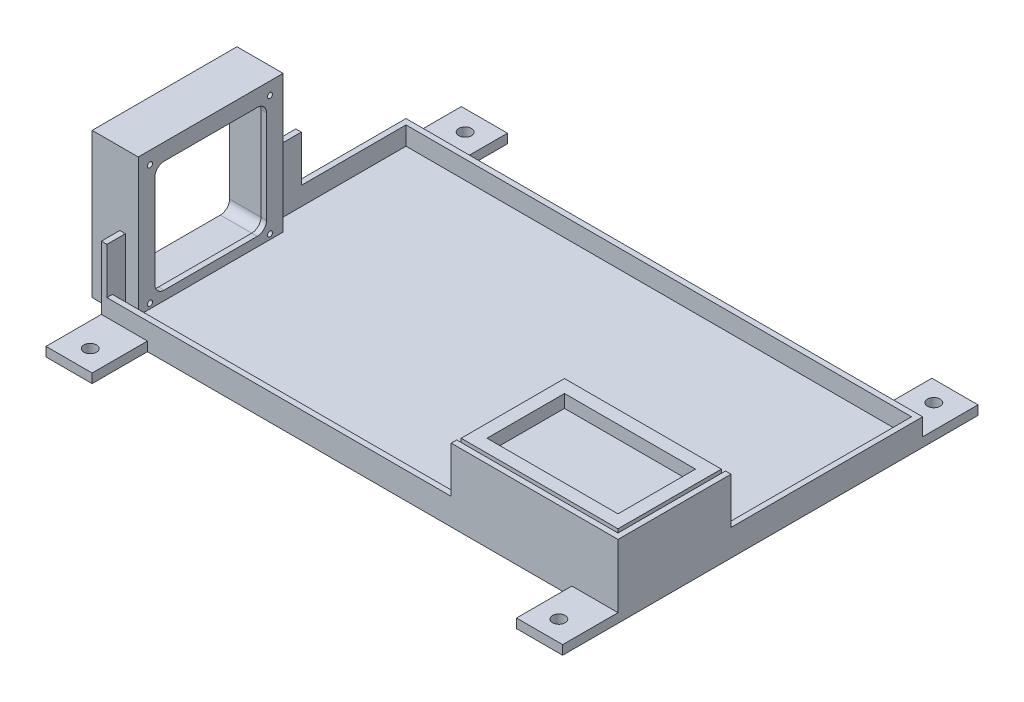
SolidWorks part; units mm, degrees
ref_plane "Front Plane" through (0, 0, 0) normal (0, 0, 1) x (1, 0, 0)
ref_plane "Top Plane" through (0, 0, 0) normal (0, 1, 0) x (1, 0, 0)
ref_plane "Right Plane" through (0, 0, 0) normal (1, 0, 0) x (0, 0, -1)
sketch "Sketch1" plane through (0, 0, 0) normal (0, 1, 0) x (1, 0, 0)
  line L1 (-140, -82.55) -> (140, -82.55)
  line L2 (-140, -82.55) -> (-140, 82.55)
  line L3 (-140, 82.55) -> (140, 82.55)
  line L4 (140, -82.55) -> (140, 82.55)
  line L5 (-140, -82.55) -> (140, 82.55) construction
  line L6 (-140, 82.55) -> (140, -82.55) construction
  point P0 (0, 0)
  dimension "D1" = 165.1
  dimension "D2" = 280
extrude "Floor" add sketch "Sketch1" along normal blind 4.3805
sketch "Sketch2" plane through (0, 4.3805, 0) normal (0, 1, 0) x (1, 0, 0)
  line L0 (137, -79.55) -> (137, 79.55)
  line L1 (137, 79.55) -> (-137, 79.55)
  line L2 (-137, 79.55) -> (-137, -79.55)
  line L3 (-137, -79.55) -> (137, -79.55)
  line L4 (140, -82.55) -> (140, 82.55)
  line L5 (140, 82.55) -> (-140, 82.55)
  line L6 (-140, 82.55) -> (-140, -82.55)
  line L7 (-140, -82.55) -> (140, -82.55)
  line L8 (140, -82.55) -> (140, 82.55)
  line L9 (140, 82.55) -> (-140, 82.55)
  line L10 (-140, 82.55) -> (-140, -82.55)
  line L11 (-140, -82.55) -> (140, -82.55)
  dimension "D1" = 0
  dimension "D2" = 3
extrude "Wall" add sketch "Sketch2" along normal blind 10
sketch "Sketch4" plane through (0, 4.3805, 0) normal (0, 1, 0) x (1, 0, 0)
  line L0 (130, -30.55) -> (59, -30.55)
  line L1 (137, -79.55) -> (52, -79.55)
  line L2 (137, -79.55) -> (137, -23.55)
  line L3 (137, -23.55) -> (52, -23.55)
  line L4 (52, -79.55) -> (52, -23.55)
  line L5 (59, -72.55) -> (59, -30.55)
  line L6 (130, -72.55) -> (59, -72.55)
  line L7 (130, -72.55) -> (130, -30.55)
  dimension "D1" = 85
  dimension "D2" = 56
  dimension "D3" = 7
extrude "Rpi stand" add sketch "Sketch4" along normal blind 7 from offset 30
sketch "Sketch7" plane through (0, 14.3805, 0) normal (0, 1, 0) x (1, 0, 0)
  line L0 (-137, 79.55) -> (-137, -79.55) construction
  line L1 (-140, -82.55) -> (-137, -82.55)
  line L2 (-140, -82.55) -> (-140, 22.7839)
  line L3 (-140, 22.7839) -> (-137, 22.7839)
  line L4 (-137, -82.55) -> (-137, 22.7839)
  line L5 (-137, -79.55) -> (137, -79.55) construction
  line L6 (140, -82.55) -> (49.6123, -82.55)
  line L7 (140, -82.55) -> (140, -79.55)
  line L8 (137, -79.55) -> (49.6123, -79.55)
  line L9 (49.6123, -82.55) -> (49.6123, -79.55)
  line L10 (137, -79.55) -> (137, 79.55) construction
  line L12 (140, -79.55) -> (140, -21.3069)
  line L13 (140, -21.3069) -> (137, -21.3069)
  line L14 (137, -79.55) -> (137, -21.3069)
  line L15 (-137, -79.55) -> (137, -79.55) construction
extrude "Temp support" add sketch "Sketch7" along normal blind 25
sketch "Sketch3" plane through (0, 0, 0) normal (0, 1, 0) x (1, 0, 0)
  line L0 (-127, 101.6) -> (127, 101.6) construction
  line L1 (-140, 82.55) -> (-115, 82.55)
  line L2 (-140, 82.55) -> (-140, 112.55)
  line L3 (-140, 112.55) -> (-115, 112.55)
  line L4 (-115, 82.55) -> (-115, 112.55)
  line L5 (140, 82.55) -> (115, 82.55)
  line L6 (140, 82.55) -> (140, 112.55)
  line L7 (140, 112.55) -> (115, 112.55)
  line L8 (115, 82.55) -> (115, 112.55)
  line L9 (-140, -82.55) -> (-115, -82.55)
  line L10 (-140, -82.55) -> (-140, -112.55)
  line L11 (-140, -112.55) -> (-115, -112.55)
  line L12 (-115, -82.55) -> (-115, -112.55)
  line L13 (140, -82.55) -> (115, -82.55)
  line L14 (140, -82.55) -> (140, -112.55)
  line L15 (140, -112.55) -> (115, -112.55)
  line L16 (115, -82.55) -> (115, -112.55)
  line L17 (127, 101.6) -> (127, -101.6) construction
  line L18 (127, -101.6) -> (-127, -101.6) construction
  line L19 (-127, -101.6) -> (-127, 101.6) construction
  line L20 (-140, 30.6215) -> (140, 30.6215) construction
  line L22 (140, -21.3069) -> (140, 82.55) construction
  line L23 (0, 101.6) -> (0, -101.6) construction
  line L24 (-140, 22.7839) -> (-140, -82.55) construction
  line L25 (140, -21.3069) -> (140, 82.55) construction
  line L26 (-137, -82.55) -> (49.6123, -82.55) construction
  circle A0 centre (-127, 101.6) radius 3.429
  circle A1 centre (127, 101.6) radius 3.429
  circle A2 centre (127, -101.6) radius 3.429
  circle A3 centre (-127, -101.6) radius 3.429
  point P28 (-127.5, -82.55)
  point P29 (-115, -97.55)
  point P30 (127.5, -82.55)
  point P31 (-115, 97.55)
  dimension "D5" = 6.858
  dimension "D1" = 25
  dimension "D2" = 25
  dimension "D3" = 30
  dimension "D4" = 30
  dimension "D6" = 203.2
  dimension "D7" = 254
extrude "Brackets" add sketch "Sketch3" along normal blind 5
sketch "Sketch5" plane through (-140, 0, 0) normal (-1, 0, 0) x (0, 0, 1)
  line L0 (-5.95, 78.8805) -> (72.55, 78.8805)
  line L1 (3.05, 4.3805) -> (63.55, 4.3805)
  line L2 (-1.95, 9.3805) -> (-1.95, 69.8805)
  line L3 (3.05, 74.8805) -> (63.55, 74.8805)
  line L4 (68.55, 9.3805) -> (68.55, 69.8805)
  line L5 (72.55, 0.3805) -> (72.55, 78.8805)
  line L6 (-5.95, 0.3805) -> (72.55, 0.3805)
  line L7 (-5.95, 0.3805) -> (-5.95, 78.8805)
  line L8 (-1.95, 4.3805) -> (68.55, 4.3805) construction
  line L9 (112.55, 5) -> (112.55, 0) construction
  line L10 (-1.95, 4.3805) -> (-1.95, 74.8805) construction
  line L11 (-79.55, 4.3805) -> (79.55, 4.3805) construction
  line L12 (68.55, 4.3805) -> (68.55, 74.8805) construction
  line L13 (-1.95, 74.8805) -> (68.55, 74.8805) construction
  arc A0 (3.05, 4.3805) -> (-1.95, 9.3805) centre (3.05, 9.3805) cw
  arc A1 (63.55, 4.3805) -> (68.55, 9.3805) centre (63.55, 9.3805) ccw
  arc A2 (63.55, 74.8805) -> (68.55, 69.8805) centre (63.55, 69.8805) cw
  arc A3 (-1.95, 69.8805) -> (3.05, 74.8805) centre (3.05, 69.8805) cw
  dimension "D4" = 5
  dimension "D1" = 70.5
  dimension "D2" = 70.5
  dimension "D5" = 40
  dimension "D3" = 4
extrude "Fan Holder" add sketch "Sketch5" along normal blind 15 and the other way blind 10
sketch "Sketch8" plane through (-140, 0, 0) normal (-1, 0, 0) x (0, 0, 1)
  line L4 (-1.95, 39.3805) -> (-1.95, 9.3805)
  line L5 (3.05, 4.3805) -> (63.55, 4.3805)
  line L6 (68.55, 9.3805) -> (68.55, 39.3805)
  line L7 (68.55, 39.3805) -> (-1.95, 39.3805)
  line L8 (-1.95, 39.3805) -> (-1.95, 9.3805)
  line L9 (3.05, 4.3805) -> (63.55, 4.3805)
  line L10 (68.55, 9.3805) -> (68.55, 39.3805)
  line L15 (68.55, 39.3805) -> (-1.95, 39.3805)
  arc A2 (-1.95, 9.3805) -> (3.05, 4.3805) centre (3.05, 9.3805) ccw
  arc A3 (-1.95, 9.3805) -> (3.05, 4.3805) centre (3.05, 9.3805) ccw
  arc A4 (63.55, 4.3805) -> (68.55, 9.3805) centre (63.55, 9.3805) ccw
  arc A5 (63.55, 4.3805) -> (68.55, 9.3805) centre (63.55, 9.3805) ccw
  dimension "D1" = 0
extrude "Fan hole" cut sketch "Sketch8" against normal up to next (3 mm away)
sketch "Sketch11" plane through (-130, 0, 0) normal (-1, 0, 0) x (0, 0, 1)
  line L0 (-5.95, 39.6305) -> (72.55, 39.6305) construction
  line L1 (33.3, 78.8805) -> (33.3, 0.3805) construction
  line L3 (1.1569, 7.0548) -> (66.1569, 7.0548) construction
  line L4 (-5.95, 78.8805) -> (-5.95, 0.3805)
  line L5 (-5.95, 0.3805) -> (72.55, 0.3805)
  line L6 (72.55, 0.3805) -> (72.55, 78.8805)
  line L7 (72.55, 78.8805) -> (-5.95, 78.8805)
  line L8 (-5.95, 78.8805) -> (-5.95, 0.3805)
  line L9 (-5.95, 0.3805) -> (72.55, 0.3805)
  line L10 (72.55, 0.3805) -> (72.55, 78.8805)
  line L11 (72.55, 78.8805) -> (-5.95, 78.8805)
  line L12 (1.1569, 7.0548) -> (1.1569, 72.0548) construction
  line L13 (1.1569, 72.0548) -> (66.1569, 72.0548) construction
  line L14 (66.1569, 7.0548) -> (66.1569, 72.0548) construction
  line L15 (1.1569, 7.0548) -> (66.1569, 72.0548) construction
  line L16 (3.05, 69.8805) -> (3.05, 9.3805)
  line L17 (3.05, 9.3805) -> (63.55, 9.3805)
  line L18 (63.55, 9.3805) -> (63.55, 69.8805)
  line L19 (63.55, 69.8805) -> (3.05, 69.8805)
  line L20 (3.05, 64.8805) -> (3.05, 14.3805)
  line L21 (8.05, 9.3805) -> (58.55, 9.3805)
  line L22 (63.55, 14.3805) -> (63.55, 64.8805)
  line L23 (58.55, 69.8805) -> (8.05, 69.8805)
  line L24 (1.1569, 72.0548) -> (66.1569, 7.0548) construction
  arc A0 (3.05, 14.3805) -> (8.05, 9.3805) centre (8.05, 14.3805) ccw
  arc A1 (58.55, 9.3805) -> (63.55, 14.3805) centre (58.55, 14.3805) ccw
  arc A2 (63.55, 64.8805) -> (58.55, 69.8805) centre (58.55, 64.8805) ccw
  arc A3 (3.05, 64.8805) -> (8.05, 69.8805) centre (8.05, 64.8805) cw
  circle A4 centre (1.1569, 72.0548) radius 1.3864
  circle A5 centre (66.1569, 72.0548) radius 1.3864
  circle A6 centre (66.1569, 7.0548) radius 1.3864
  circle A7 centre (1.1569, 7.0548) radius 1.3864
  point P24 (33.6569, 39.5548)
  dimension "D3" = 5
  dimension "D4" = 65
  dimension "D5" = 65
  dimension "D1" = 0
  dimension "D2" = 9
extrude "Boss-Extrude9" add sketch "Sketch11" along normal blind 3
equation "\"D2@Sketch3\"=\"D1@Sketch3\""
equation "\"D4@Sketch3\"=\"D3@Sketch3\""
